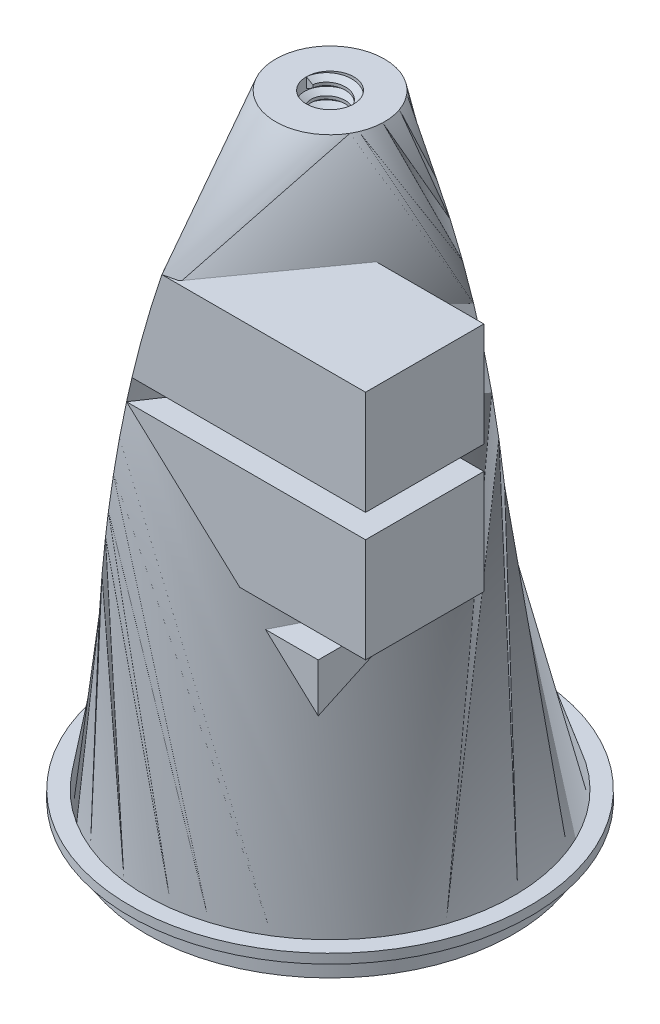
SolidWorks part; units mm, degrees
ref_plane "Front Plane" through (0, 0, 0) normal (0, 0, 1) x (1, 0, 0)
ref_plane "Top Plane" through (0, 0, 0) normal (0, 1, 0) x (1, 0, 0)
ref_plane "Right Plane" through (0, 0, 0) normal (1, 0, 0) x (0, 0, -1)
sketch "Sketch1" plane through (0, 0, 0) normal (0, 1, 0) x (1, 0, 0)
  circle A0 centre (0, 0) radius 38.85
  dimension "D1" = 77.7
extrude "Boss-Extrude1" add sketch "Sketch1" along normal blind 5
sketch "Sketch4" plane through (0, 0, 0) normal (0, 0, 1) x (1, 0, 0)
  line L0 (0, 5) -> (0, 7)
  line L1 (-39.35, 7) -> (-42.35, 7)
  line L2 (-42.35, 5) -> (0, 5)
  line L4 (0, 135) -> (0, 150) construction
  line L5 (38.85, 5) -> (-38.85, 5) construction
  line L6 (0, 7) -> (-39.35, 7) construction
  line L7 (0, 135) -> (-12, 135) construction
  line L8 (-42.35, 7) -> (-42.35, 5)
  line L9 (-39.35, 7) -> (-38.85, 7)
  line L10 (-12, 135) -> (-11.5, 135) construction
  line L11 (-11.5, 135) -> (0, 135)
  line L12 (0, 135) -> (0, 7)
  arc A0 (-15, 135) -> (-42.35, 5) centre (257.6121, 9.7696) ccw construction
  arc A1 (-15, 135) -> (0, 150) centre (27.0507, 107.9493) cw construction
  arc A2 (-39.35, 7) -> (-12, 135) centre (260.6367, 9.8232) cw construction
  arc A3 (-11.5, 135) -> (-38.85, 7) centre (261.1367, 9.8232) ccw
  dimension "D4" = 300
  dimension "D7" = 50
  dimension "D1" = 15
  dimension "D2" = 5
  dimension "D3" = 42.35
  dimension "D5" = 130
  dimension "D6" = 15
  dimension "D8" = 3
  dimension "D9" = 3
  dimension "D10" = 2
  dimension "D11" = 42.35
  dimension "D12" = 0.5
  dimension "D13" = 0.5
revolve "Revolve2" add sketch "Sketch4" angle 360 about L0
sketch "Sketch5" plane through (0, 0, 0) normal (1, 0, 0) x (0, 0, -1)
  line L0 (0, 135) -> (0, 7) construction
  line L1 (12.5, 69) -> (-12.5, 69)
  line L2 (12.5, 69) -> (12.5, 47)
  line L3 (12.5, 47) -> (-12.5, 47)
  line L4 (-12.5, 69) -> (-12.5, 47)
  line L5 (12.5, 69) -> (-12.5, 47) construction
  line L6 (12.5, 47) -> (-12.5, 69) construction
  line L7 (12.5, 96) -> (-12.5, 96)
  line L8 (12.5, 96) -> (12.5, 74)
  line L9 (12.5, 74) -> (-12.5, 74)
  line L10 (-12.5, 96) -> (-12.5, 74)
  line L11 (12.5, 96) -> (-12.5, 74) construction
  line L12 (12.5, 74) -> (-12.5, 96) construction
  line L13 (12.5, 42) -> (-12.5, 42)
  line L14 (12.5, 42) -> (12.5, 20)
  line L15 (12.5, 20) -> (-12.5, 20)
  line L16 (-12.5, 42) -> (-12.5, 20)
  line L17 (12.5, 42) -> (-12.5, 20) construction
  line L18 (12.5, 20) -> (-12.5, 42) construction
  point P0 (0, 58)
  point P7 (0, 26.3644)
  point P8 (0, 85)
  point P13 (0, 31)
  point P18 (0, 0)
  point P19 (0, 99.5793)
  point P20 (0, 63.3902)
  point P21 (0, 92.6761)
  dimension "D1" = 25
  dimension "D2" = 22
  dimension "D3" = 25
  dimension "D4" = 22
  dimension "D5" = 25
  dimension "D6" = 22
  dimension "D7" = 5
  dimension "D8" = 5
  dimension "D9" = 20
extrude "Cut-Extrude1" cut sketch "Sketch5" against normal blind 40 and the other way blind 10
sketch "Sketch6" plane through (10, 0, 0) normal (-1, 0, 0) x (0, 0, 1)
  line L4 (12.5, 47) -> (12.5, 69)
  line L5 (12.5, 69) -> (-12.5, 69)
  line L6 (-12.5, 69) -> (-12.5, 47)
  line L7 (-12.5, 47) -> (12.5, 47)
  line L8 (12.5, 47) -> (12.5, 69)
  line L9 (12.5, 69) -> (-12.5, 69)
  line L10 (-12.5, 69) -> (-12.5, 47)
  line L11 (-12.5, 47) -> (12.5, 47)
  dimension "D1" = 0
extrude "Cut-Extrude2" cut sketch "Sketch6" against normal blind 10
sketch "Sketch7" plane through (10, 0, 0) normal (-1, 0, 0) x (0, 0, 1)
  line L4 (12.5, 74) -> (12.5, 96)
  line L5 (12.5, 96) -> (-12.5, 96)
  line L6 (-12.5, 96) -> (-12.5, 74)
  line L7 (-12.5, 74) -> (12.5, 74)
  line L8 (12.5, 74) -> (12.5, 96)
  line L9 (12.5, 96) -> (-12.5, 96)
  line L10 (-12.5, 96) -> (-12.5, 74)
  line L11 (-12.5, 74) -> (12.5, 74)
  dimension "D1" = 0
extrude "Cut-Extrude3" cut sketch "Sketch7" against normal blind 10
sketch "Sketch8" plane through (0, 135, 0) normal (0, 1, 0) x (1, 0, 0)
  circle A0 centre (0, 0) radius 5
  dimension "D1" = 10
extrude "Cut-Extrude4" cut sketch "Sketch8" against normal blind 10
thread "Thread1" pitch 2.5 method extrude profile "Thread Profile1" start angle 0, offset 0, length 0, pitch 2.5, diameter 10
ref_plane "Plane1" through (-5, 135, 0) normal (0, 0, 1) x (-1, 0, 0)
sketch "Thread Profile1" plane through (-5, 135, 0) normal (0, 0, 1) x (-1, 0, 0)
  line L0 (0, 0) -> (0, 2.5) construction
  line L11 (0, 0) -> (0, 2.1875)
  line L12 (0, 2.1875) -> (-1.3532, 1.4062)
  line L13 (-1.3532, 1.4062) -> (-1.3532, 0.7812)
  line L15 (-1.3532, 0.7812) -> (0, 0)
  line L17 (-1.3532, 1.0937) -> (0, 1.0937) construction
  point P2 (0, 0)
  dimension "Pitch" = 2.5
  dimension "Profile_Angle" = 60
  dimension "Profile_Land" = 0.625
  dimension "Profile_Height" = 1.3532
